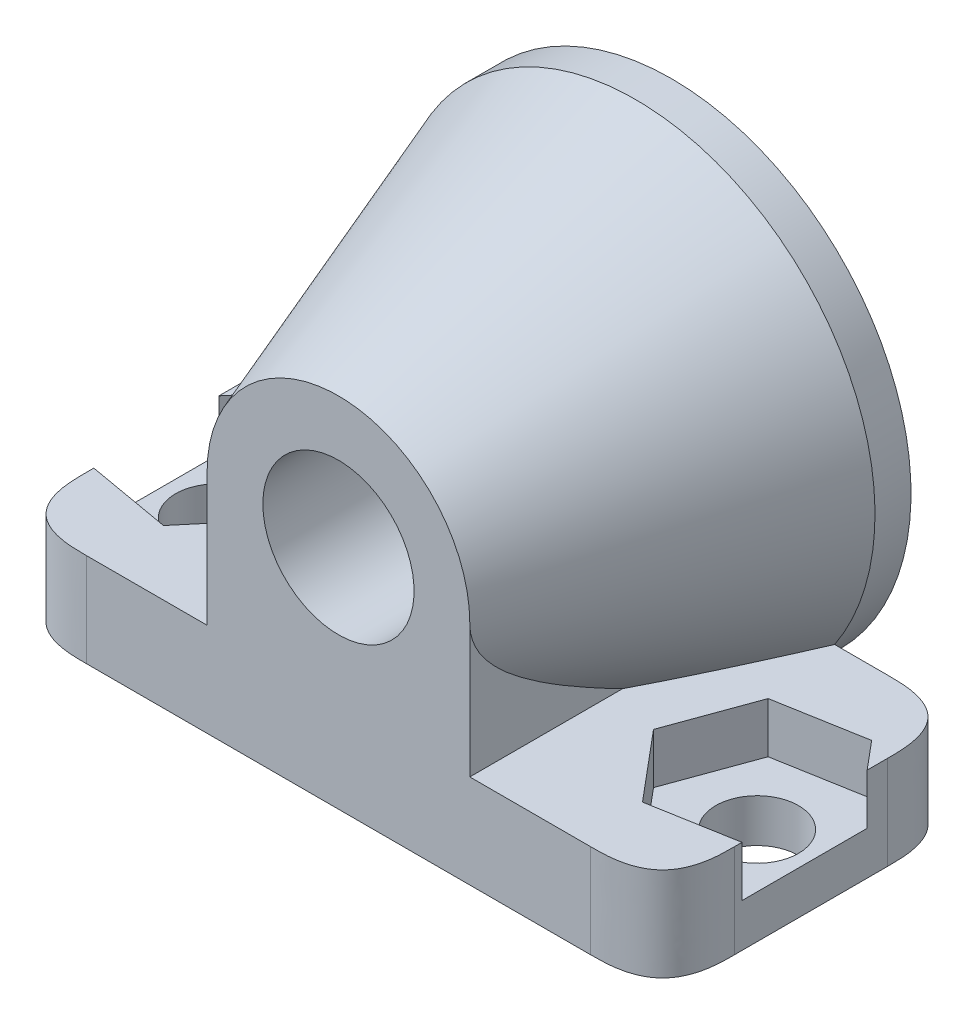
SolidWorks part; units mm, degrees
material "Nylon 101"
ref_plane "Front" through (0, 0, 0) normal (0, 0, 1) x (1, 0, 0)
ref_plane "Top" through (0, 0, 0) normal (0, 1, 0) x (1, 0, 0)
ref_plane "Right" through (0, 0, 0) normal (1, 0, 0) x (0, 0, -1)
ref_axis "X" through (-80.9, 0, 0) along (1, 0, 0)
ref_axis "Y" through (0, -10.2647, 0) along (0, 1, 0)
ref_axis "Z" through (0, 0, -80.9) along (0, 0, 1)
sketch "Sketch1" plane through (0, 0, 0) normal (0, 0, 1) x (1, 0, 0)
  line L7 (0, 0) -> (0, -6.295) construction
  circle A0 centre (0, 0) radius 6.65
  dimension "D1" = 13.3
  dimension "D2" = 6.295
extrude "Boss-Extrude1" add sketch "Sketch1" along normal blind 8.25 draft 20
sketch "Sketch2" plane through (0, 0, 0) normal (0, 0, -1) x (-1, 0, 0)
  circle A0 centre (0, 0) radius 5.45
  circle A1 centre (0, 0) radius 6.65
  dimension "D1" = 10.9
  dimension "D2" = 13.3
extrude "Boss-Extrude2" add sketch "Sketch2" along normal blind 1
sketch "Sketch3" plane through (0, 0, 0) normal (0, 0, -1) x (-1, 0, 0)
  circle A0 centre (0, 0) radius 2.1
  dimension "D1" = 4.2
extrude "Cut-Extrude1" cut sketch "Sketch3" against normal through all
sketch "Sketch4" plane through (0, 0, 0) normal (0, 0, 1) x (1, 0, 0)
  line L0 (7.5, -6.295) -> (-7.5, -6.295)
  line L1 (-7.5, -6.295) -> (-7.5, -11.295)
  line L2 (-7.5, -11.295) -> (7.5, -11.295)
  line L3 (7.5, -11.295) -> (7.5, -6.295)
  line L4 (0, 0) -> (0, -6.295) construction
  dimension "D1" = 6.295
  dimension "D2" = 5
  dimension "D3" = 15
extrude "Cut-Extrude2" cut sketch "Sketch4" against normal through all both and the other way through all
sketch "Sketch5" plane through (0, 0, 0) normal (0, 0, 1) x (1, 0, 0)
  line L0 (3.6472, 0) -> (3.6472, -3.695)
  line L1 (3.6472, -3.695) -> (9, -3.695)
  line L2 (9, -3.695) -> (9, -6.295)
  line L3 (9, -6.295) -> (-9, -6.295)
  line L4 (-9, -6.295) -> (-9, -3.695)
  line L5 (-9, -3.695) -> (-3.6472, -3.695)
  line L6 (-3.6472, -3.695) -> (-3.6472, 0)
  line L7 (0, 0) -> (0, -6.295) construction
  line L8 (2.1437, -6.295) -> (-2.1437, -6.295) construction
  arc A0 (3.6472, 0) -> (-3.6472, 0) centre (0, 0) ccw
  circle A1 centre (0, 0) radius 2.1
  circle A3 centre (0, 0) radius 2.1 construction
  circle A4 centre (0, 0) radius 3.6472 construction
  dimension "D1" = 2.6
  dimension "D3" = 18
extrude "Boss-Extrude3" add sketch "Sketch5" along normal up to surface (8.25 mm away) up to face at (-2.1, 0, 8.25)
sketch "Sketch6" plane through (0, -6.295, 0) normal (0, -1, 0) x (1, 0, 0)
  line L0 (-7.5, 4.125) -> (7.5, 4.125) construction
  line L1 (-6.6509, 6.4579) -> (-9.0958, 6.0268)
  line L2 (-9.0958, 6.0268) -> (-9.9449, 3.6939)
  line L3 (-9.9449, 3.6939) -> (-8.3491, 1.7921)
  line L4 (-8.3491, 1.7921) -> (-5.9042, 2.2232)
  line L5 (-5.9042, 2.2232) -> (-5.0551, 4.5561)
  line L6 (-5.0551, 4.5561) -> (-6.6509, 6.4579)
  line L7 (6.6509, 6.4579) -> (5.0551, 4.5561)
  line L8 (5.0551, 4.5561) -> (5.9042, 2.2232)
  line L9 (5.9042, 2.2232) -> (8.3491, 1.7921)
  line L10 (8.3491, 1.7921) -> (9.9449, 3.6939)
  line L11 (9.9449, 3.6939) -> (9.0958, 6.0268)
  line L12 (9.0958, 6.0268) -> (6.6509, 6.4579)
  line L13 (0, 0) -> (0, 4.125) construction
  line L14 (0, 4.125) -> (0, 8.25) construction
  line L15 (3.6472, 8.25) -> (-3.6472, 8.25) construction
  circle A0 centre (-7.5, 4.125) radius 2.15 construction
  circle A1 centre (7.5, 4.125) radius 2.15 construction
  dimension "D1" = 4.3
  dimension "D2" = 15
  dimension "D3" = 70
  dimension "D4" = 70
extrude "Cut-Extrude3" cut sketch "Sketch6" against normal up to next from offset 1.2 offset against normal yes
sketch "Sketch7" plane through (0, -6.295, 0) normal (0, -1, 0) x (1, 0, 0)
  circle A0 centre (7.5, 4.125) radius 1.15
  circle A1 centre (-7.5, 4.125) radius 1.15
  dimension "D1" = 2.3
extrude "Cut-Extrude4" cut sketch "Sketch7" against normal up to next
fillet "Fillet1" radius 2 4 edges at (9, -4.995, 0) (9, -4.995, 8.25) (-9, -4.995, 0) (-9, -4.995, 8.25) curvature continuous yes
